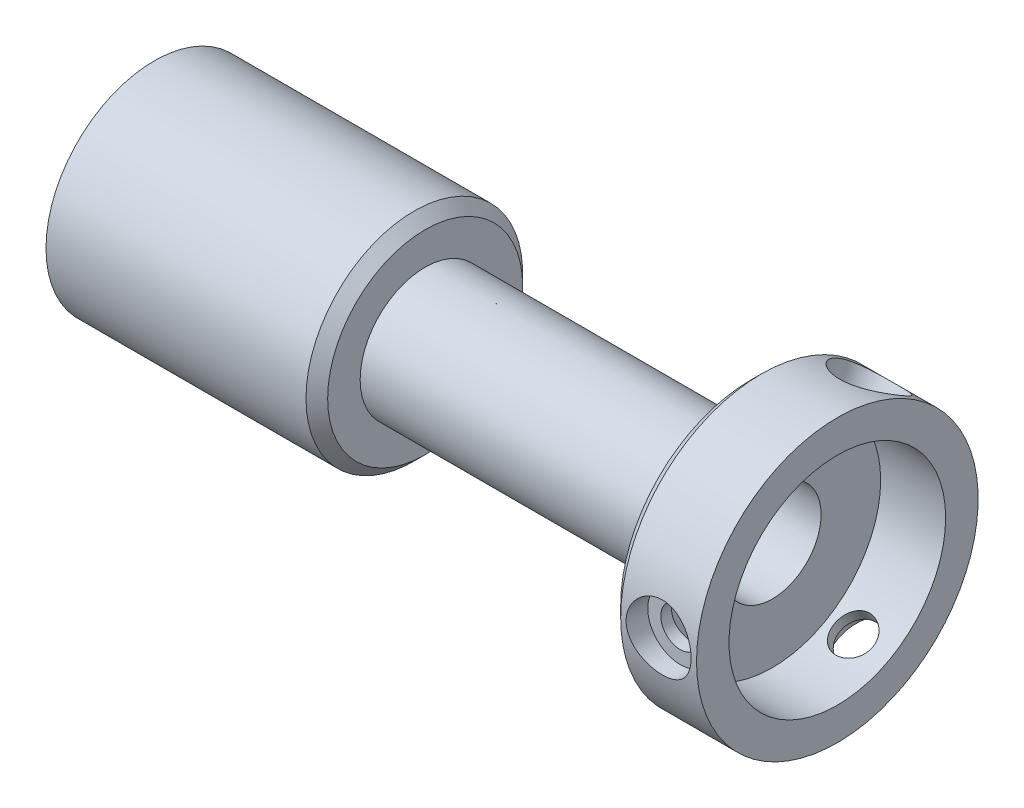
SolidWorks part; units mm, degrees
ref_plane "前视基准面" through (0, 0, 0) normal (0, 0, 1) x (1, 0, 0)
ref_plane "上视基准面" through (0, 0, 0) normal (0, 1, 0) x (1, 0, 0)
ref_plane "右视基准面" through (0, 0, 0) normal (1, 0, 0) x (0, 0, -1)
sketch "草图1" plane through (0, 0, 0) normal (0, 0, 1) x (1, 0, 0)
  line L0 (-26.1648, 0) -> (37.5232, 0) construction
  line L1 (0, 0) -> (0, 10)
  line L2 (0, 10) -> (25, 10)
  line L3 (25, 10) -> (25, 6)
  line L4 (25, 6) -> (55.05, 6)
  line L5 (55.05, 6) -> (55.05, 13)
  line L6 (55.05, 13) -> (63.05, 13)
  line L7 (63.05, 13) -> (63.05, 0)
  line L8 (63.05, 0) -> (0, 0)
  dimension "D1" = 10
  dimension "D2" = 4
  dimension "D3" = 13
  dimension "D4" = 25
  dimension "D5" = 63.05
  dimension "D6" = 8
revolve "旋转1" add sketch "草图1" angle 360 about L0
sketch "草图2" plane through (63.05, 0, 0) normal (1, 0, 0) x (0, 0, -1)
  circle A0 centre (0, 0) radius 10
  dimension "D1" = 20
extrude "切除-拉伸1" cut sketch "草图2" against normal offset from surface (6 mm away) 2 up to face at (55.05, 0, 6)
sketch "草图3" plane through (0, 0, 0) normal (-1, 0, 0) x (0, 0, 1)
  circle A0 centre (0, 0) radius 4.5
  dimension "D1" = 9
extrude "切除-拉伸2" cut sketch "草图3" against normal through all
ref_plane "基准面1" through (0, 0, 13) normal (0, 0, 1) x (1, 0, 0)
hole_wizard "打孔尺寸(%根据)内六角圆柱头螺钉的类型1" positions "草图5" profile "草图4" counterbore size "M3" standard "GB" end condition up to next
sketch "草图5" plane through (0, 0, 13) normal (0, 0, 1) x (1, 0, 0)
  line L0 (59.55, 18.6777) -> (59.55, -21.7042) construction
  line L2 (0, 0) -> (75.0669, 0) construction
  line L4 (55.05, 13) -> (55.05, -13) construction
  point P0 (59.55, 0)
  dimension "D1" = 4.5
sketch "草图4" plane through (59.55, 0, 13) normal (1, 0, 0) x (0, -1, 0)
  line L0 (0, 0) -> (0, 26)
  line L1 (0, 26) -> (1.8, 26)
  line L3 (1.8, 26) -> (1.8, 2)
  line L4 (1.8, 2) -> (3, 2)
  line L5 (3, 2) -> (3, 0)
  line L7 (3, 0) -> (0, 0)
  line L11 (0, -6.35) -> (0, 107.95) construction
  dimension "通孔孔直径" = 3.6
  dimension "通孔孔深度" = 26
  dimension "柱形沉头孔直径" = 6
  dimension "柱形沉头孔深度" = 2
ref_axis "基准轴1" through (63.05, 0, 0) along (-1, 0, 0)
pattern_circular "阵列(圆周)1" count 3 over 360 about axis through (63.05, 0, 0) along (-1, 0, 0) of "打孔尺寸(%根据)内六角圆柱头螺钉的类型1"
hole_wizard "M3 螺纹孔1" positions "草图11" profile "草图10" tap size "M3" standard "GB"
sketch "草图11" plane through (0, 0, 0) normal (-1, 0, 0) x (0, 0, 1)
  line L0 (0, 0) -> (0, 14.127) construction
  circle A0 centre (0, 0) radius 7.5 construction
  point P0 (0, 7.5)
  dimension "D1" = 15
sketch "草图10" plane through (0, 7.5, 0) normal (0, 1, 0) x (0, 0, 1)
  line L0 (0, 0) -> (0, 8.2511)
  line L1 (0, 8.2511) -> (1.25, 7.5)
  line L2 (1.25, 7.5) -> (1.25, 0)
  line L5 (1.25, 0) -> (0, 0)
  line L10 (0, 8.2511) -> (-1.25, 7.5) construction
  line L11 (0, -6.35) -> (0, 107.95) construction
  dimension "螺纹孔钻头直径" = 2.5
  dimension "螺纹孔钻头深度" = 7.5
  dimension "导头角度" = 118
cosmetic thread "孔螺蚊线1" parameters "D1"=6, "D2"=3
ref_axis "基准轴2" through (25, 0, 0) along (-1, 0, 0)
pattern_circular "阵列(圆周)2" count 6 over 360 about axis through (25, 0, 0) along (-1, 0, 0) of "M3 螺纹孔1"
chamfer "倒角1" distance 1 angle 45 2 edges at (25, 0, 10) (55.05, 0, 13)
